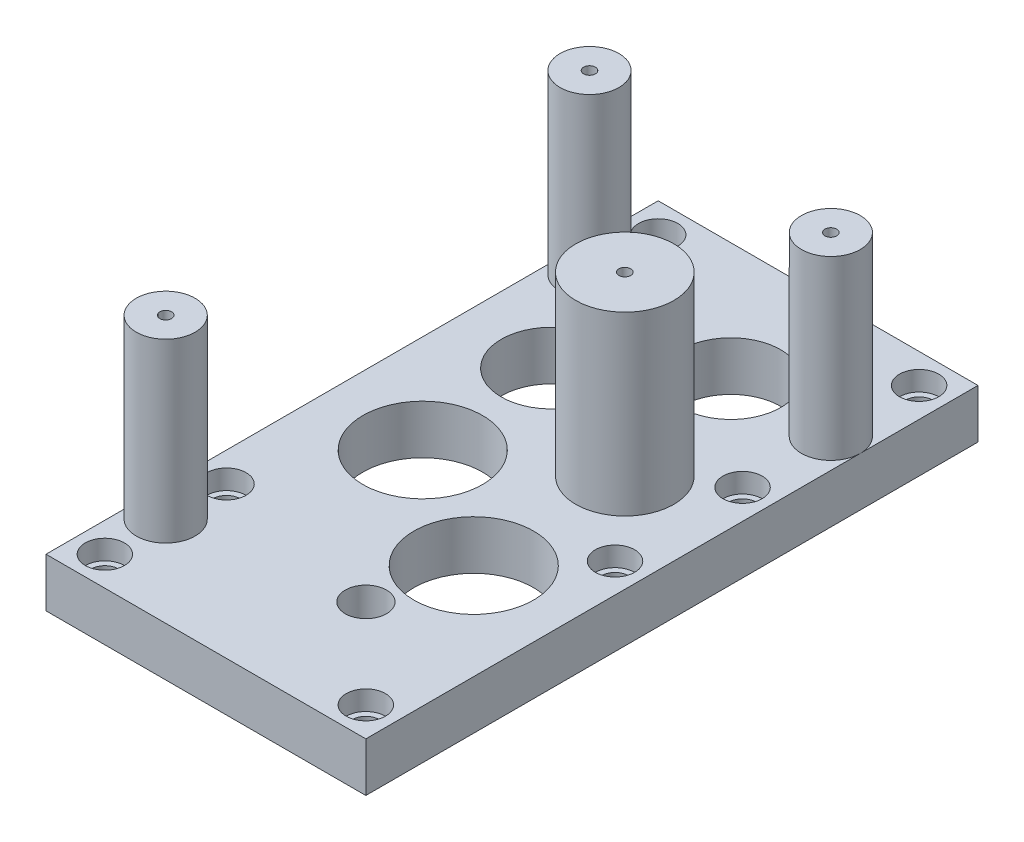
SolidWorks part; units mm, degrees
ref_plane "前视基准面" through (0, 0, 0) normal (0, 0, 1) x (1, 0, 0)
ref_plane "上视基准面" through (0, 0, 0) normal (0, 1, 0) x (1, 0, 0)
ref_plane "右视基准面" through (0, 0, 0) normal (1, 0, 0) x (0, 0, -1)
other "Configuration Table"
sketch "草图1" plane through (0, 0, 0) normal (0, 1, 0) x (1, 0, 0)
  line L1 (-5, 17) -> (11.3, 17)
  line L2 (-5, 17) -> (-5, -14.2)
  line L3 (-5, -14.2) -> (11.3, -14.2)
  line L4 (11.3, 17) -> (11.3, -14.2)
  circle A0 centre (0, 0) radius 3.05
  circle A1 centre (5.2565, -8.1523) radius 1.05
  circle A2 centre (6.4, -3.8) radius 3.05
  circle A3 centre (-0.3371, 6.8918) radius 2.55
  circle A4 centre (4.7, 11) radius 2.55
  dimension "D1" = 6.1
  dimension "D2" = 2.1
  dimension "D6" = 5.1
  dimension "D7" = 5.1
  dimension "D3" = 4.5
  dimension "D4" = 9.7
  dimension "D5" = 6.9
  dimension "D8" = 6.5
  dimension "D9" = 11
  dimension "D10" = 6.4
  dimension "D11" = 3.8
  dimension "D12" = 4.7
  dimension "D13" = 17
  dimension "D14" = 5
  dimension "D15" = 14.2
  dimension "D16" = 11.3
extrude "凸台-拉伸1" add sketch "草图1" along normal blind 2.5 contours L4 L3 L2 L1 | A3 | A0 | A1 | A2 | A4
sketch "草图2" plane through (0, 2.5, 0) normal (0, 1, 0) x (1, 0, 0)
  line L0 (-5, 17) -> (11.3, 17) construction
  line L3 (-5, 17) -> (-5, -14.2) construction
  line L4 (11.3, 17) -> (11.3, -14.2) construction
  line L5 (-5, -14.2) -> (11.3, -14.2) construction
  circle A0 centre (9.8, 15.5) radius 0.7
  circle A1 centre (-3.5, 15.5) radius 1
  circle A2 centre (-3.5, -12.7) radius 1
  circle A3 centre (9.8, -12.7) radius 1
  circle A4 centre (9.8, -12.7) radius 0.7
  circle A5 centre (-3.5, -12.7) radius 0.7
  circle A6 centre (-3.5, 15.5) radius 0.7
  circle A7 centre (9.8, 15.5) radius 1
  circle A8 centre (-3.5, -6.5) radius 1
  circle A9 centre (-3.5, -6.5) radius 0.7
  circle A10 centre (9.8, 0) radius 1
  circle A11 centre (9.8, 0) radius 0.7
  circle A12 centre (9.8, 6.5) radius 1
  circle A13 centre (9.8, 6.5) radius 0.7
  circle A14 centre (-3.5, 6.5) radius 1
  circle A15 centre (-3.5, 6.5) radius 0.7
  dimension "D1" = 1.4
  dimension "D2" = 2
  dimension "D3" = 1.5
  dimension "D4" = 1.5
  dimension "D5" = 1.5
  dimension "D6" = 1.5
  dimension "D7" = 1.5
  dimension "D8" = 1.5
  dimension "D9" = 10.5
  dimension "D10" = 10.5
  dimension "D11" = 1.5
  dimension "D12" = 1.5
  dimension "D13" = 1.5
  dimension "D14" = 1.5
  dimension "D15" = 1.5
  dimension "D16" = 1.5
  dimension "D17" = 7.7
  dimension "D18" = 14.2
extrude "切除-拉伸1" cut sketch "草图2" against normal blind 1 contours A2 | A3 | A8 | A10 | A12 | A1 | A7
extrude "切除-拉伸2" cut sketch "草图2<3>" against normal through all contours A5 | A9 | A4 | A11 | A13 | A0 | A6
sketch "草图2<3>" plane through (0, 2.5, 0) normal (0, 1, 0) x (1, 0, 0) same geometry as "草图2"
sketch "草图3" plane through (0, 2.5, 0) normal (0, 1, 0) x (1, 0, 0)
  line L0 (-5, 17) -> (-5, -14.2) construction
  line L2 (-3.5, -6.5) -> (-3.5, -12.7) construction
  line L3 (9.8, 15.5) -> (9.8, 6.5) construction
  line L4 (11.3, 17) -> (11.3, -14.2) construction
  line L5 (-5, 17) -> (11.3, 17) construction
  circle A0 centre (-3.5, -9.6) radius 1.5
  circle A1 centre (-3.5, -9.6) radius 0.3
  circle A2 centre (-3.5, 12) radius 1.5
  circle A3 centre (-3.5, 12) radius 0.3
  circle A4 centre (6.3, 4) radius 2.5
  circle A5 centre (6.3, 4) radius 0.3
  circle A6 centre (9.8, 11) radius 1.5
  circle A7 centre (9.8, 11) radius 0.3
  dimension "D1" = 0.6
  dimension "D2" = 5
  dimension "D3" = 5
  dimension "D4" = 13
  dimension "D5" = 5
extrude "凸台-拉伸2" add sketch "草图3" along normal blind 9 contours A0 | A4 | A6 | A2
extrude "切除-拉伸3" cut sketch "草图3<3>" against normal blind 2 from surface contours A3 | A7 | A5 | A1 starting at face at (-3.5, 11.5, -10.5)
sketch "草图3<3>" plane through (0, 2.5, 0) normal (0, 1, 0) x (1, 0, 0) same geometry as "草图3"
sketch "草图4" plane through (0, 0, -17) normal (0, 0, -1) x (-1, 0, 0)
  circle A2 centre (0.8, 1.1873) radius 0.3
  circle A3 centre (-4.2, 1.1873) radius 0.3
  dimension "D1" = 0.6
extrude "切除-拉伸4" cut sketch "草图4" against normal blind 2
